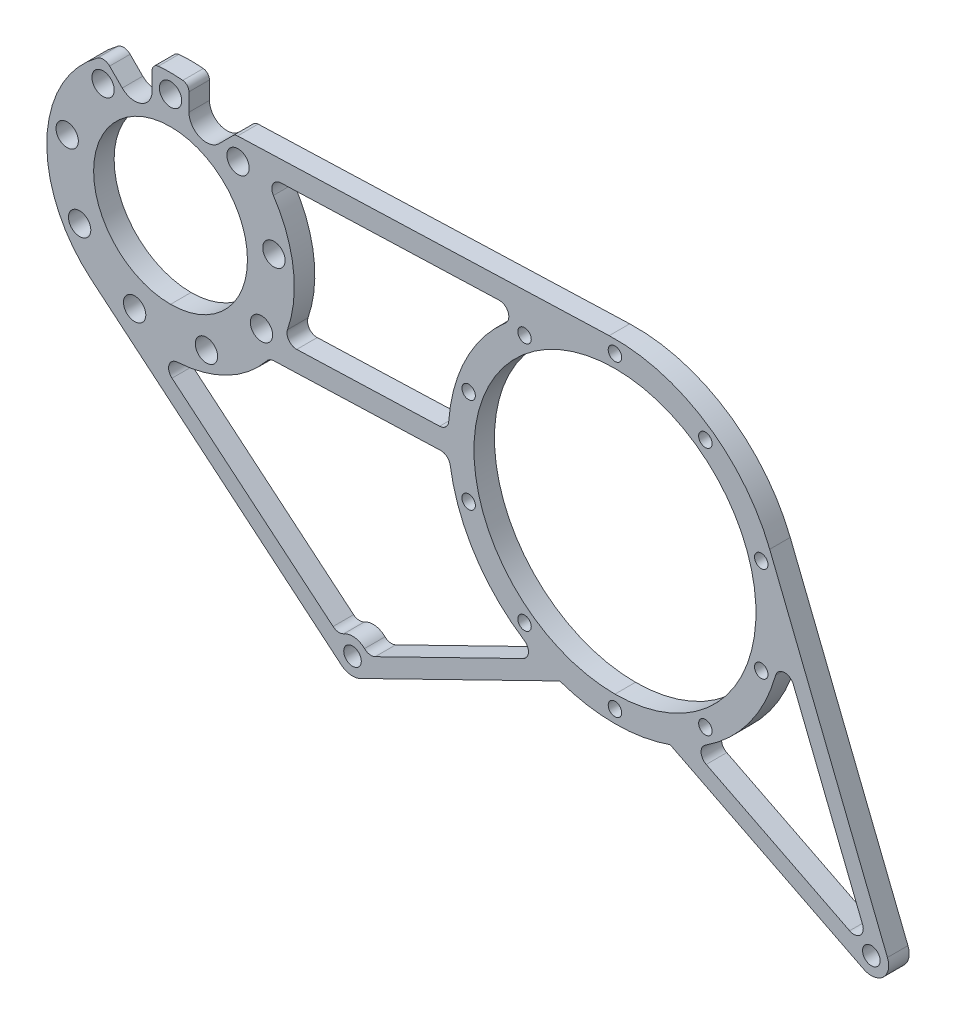
SolidWorks part; units mm, degrees
material "6061-T6 (SS)"
ref_plane "Front Plane" through (0, 0, 0) normal (0, 0, 1) x (1, 0, 0)
ref_plane "Top Plane" through (0, 0, 0) normal (0, 1, 0) x (1, 0, 0)
ref_plane "Right Plane" through (0, 0, 0) normal (1, 0, 0) x (0, 0, -1)
sketch "Sketch2" plane through (0, 0, 0) normal (0, 0, 1) x (1, 0, 0)
  line L0 (-114.3, 107.95) -> (-114.3, 95.25) construction
  line L1 (-308.8661, 91.7104) -> (-215.9264, 14.1075)
  line L3 (-13.0706, 21.4387) -> (-56.8054, 130.918)
  line L4 (-208.9705, 13.2659) -> (-134.815, 49.5352)
  line L5 (-21.9498, 13.301) -> (-93.785, 49.5352)
  line L7 (-254.4917, 165.0591) -> (-116.4363, 169.8256)
  line L10 (-286.2388, 170.2207) -> (-286.2388, 163.648)
  line L11 (-299.2388, 163.648) -> (-299.2388, 164.225)
  line L12 (-256.2001, 164.3167) -> (-261.465, 159.0518)
  line L13 (-272.5612, 163.648) -> (-272.5612, 170.2207)
  line L14 (-286.2388, 170.2207) -> (-286.2388, 163.648)
  line L16 (-256.2001, 164.3167) -> (-261.465, 159.0518)
  line L17 (-272.5612, 163.648) -> (-272.5612, 170.2207)
  line L84 (-302.5999, 164.3167) -> (-297.335, 159.0518) construction
  line L85 (-302.028, 163.7448) -> (-297.335, 159.0518)
  circle A0 centre (-279.4, 127) radius 28.575
  circle A1 centre (-114.3, 95.25) radius 36 construction
  circle A2 centre (0, 0) radius 12.7 construction
  circle A3 centre (-228.6, 0) radius 12.7 construction
  arc A5 (-134.815, 49.5352) -> (-93.785, 49.5352) centre (-114.3, 107.95) ccw
  circle A6 centre (-19.05, 19.05) radius 3.2639
  circle A7 centre (-211.7995, 19.05) radius 3.2639
  arc A8 (-215.9264, 14.1075) -> (-208.9705, 13.2659) centre (-211.7995, 19.05) ccw
  arc A9 (-21.9498, 13.301) -> (-13.0706, 21.4387) centre (-19.05, 19.05) ccw
  circle A10 centre (-114.3, 107.95) radius 52.3875
  arc A11 (-56.8054, 130.918) -> (-116.4363, 169.8256) centre (-114.3, 107.95) ccw
  arc A12 (-134.815, 49.5352) -> (-116.4363, 169.8256) centre (-114.3, 107.95) ccw construction
  arc A13 (-308.8661, 91.7104) -> (-306.5609, 164.0931) centre (-279.4, 127) cw
  arc A20 (-299.2388, 163.648) -> (-286.2388, 163.648) centre (-292.7388, 163.648) ccw
  arc A21 (-299.2388, 164.225) -> (-303.0875, 166.4019) centre (-301.7788, 164.225) ccw
  arc A22 (-303.0875, 166.4019) -> (-252.9423, 164.5979) centre (-279.4, 127) ccw
  arc A23 (-252.9423, 164.5979) -> (-256.2001, 164.3167) centre (-254.4041, 162.5207) ccw
  arc A24 (-272.5612, 163.648) -> (-261.465, 159.0518) centre (-266.0612, 163.648) ccw
  arc A25 (-272.5612, 170.2207) -> (-274.8498, 172.7483) centre (-275.1012, 170.2207) ccw
  arc A26 (-274.8498, 172.7483) -> (-283.9502, 172.7483) centre (-279.4, 127) ccw
  arc A27 (-283.9502, 172.7483) -> (-286.2388, 170.2207) centre (-283.6988, 170.2207) ccw
  arc A28 (-297.335, 159.0518) -> (-286.2388, 163.648) centre (-292.7388, 163.648) ccw
  arc A31 (-254.4917, 165.0591) -> (-256.2001, 164.3167) centre (-254.4041, 162.5207) ccw
  arc A32 (-272.5612, 163.648) -> (-261.465, 159.0518) centre (-266.0612, 163.648) ccw
  arc A33 (-272.5612, 170.2207) -> (-274.8498, 172.7483) centre (-275.1012, 170.2207) ccw
  arc A34 (-274.8498, 172.7483) -> (-283.9502, 172.7483) centre (-279.4, 127) ccw
  arc A35 (-283.9502, 172.7483) -> (-286.2388, 170.2207) centre (-283.6988, 170.2207) ccw
  arc A166 (-306.5609, 164.0931) -> (-302.028, 163.7448) centre (-304.4975, 161.2752) cw
  dimension "D1" = 25.4
  dimension "D2" = 25.4
  dimension "D8" = 57.15
  dimension "D9" = 72
  dimension "D10" = 3.4925
  dimension "D12" = 123.825
  dimension "D13" = 6.5278
  dimension "D16" = 6.5278
  dimension "D18" = 3.175
  dimension "D20" = 104.775
  dimension "D3" = 228.6
  dimension "D4" = 114.3
  dimension "D5" = 95.25
  dimension "D6" = 279.4
  dimension "D7" = 127
  dimension "D11" = 12.7
  dimension "D14" = 19.05
  dimension "D15" = 19.05
  dimension "D17" = 25.4
  dimension "D19" = 82.55
  dimension "D21" = 0
extrude "Boss-Extrude1" add sketch "Sketch2" along normal blind 7.62
sketch "Sketch3" plane through (0, 0, 7.62) normal (0, 0, 1) x (1, 0, 0)
  line L0 (-279.4, 127) -> (-279.4, 166) construction
  line L1 (-114.3, 107.95) -> (-114.3, 165.1) construction
  circle A0 centre (-279.4, 127) radius 39 construction
  circle A1 centre (-279.4, 166) radius 4.15
  circle A2 centre (-254.3313, 156.8757) radius 4.15
  circle A3 centre (-240.9925, 133.7723) radius 4.15
  circle A4 centre (-245.625, 107.5) radius 4.15
  circle A5 centre (-266.0612, 90.352) radius 4.15
  circle A6 centre (-292.7388, 90.352) radius 4.15
  circle A7 centre (-313.175, 107.5) radius 4.15
  circle A8 centre (-317.8075, 133.7723) radius 4.15
  circle A9 centre (-304.4687, 156.8757) radius 4.15
  circle A10 centre (-114.3, 107.95) radius 57.15 construction
  circle A11 centre (-114.3, 165.1) radius 2.5
  circle A12 centre (-80.7081, 154.1853) radius 2.5
  circle A13 centre (-59.9471, 125.6103) radius 2.5
  circle A14 centre (-59.9471, 90.2897) radius 2.5
  circle A15 centre (-80.7081, 61.7147) radius 2.5
  circle A16 centre (-114.3, 50.8) radius 2.5
  circle A17 centre (-147.8919, 61.7147) radius 2.5
  circle A18 centre (-168.6529, 90.2897) radius 2.5
  circle A19 centre (-168.6529, 125.6103) radius 2.5
  circle A20 centre (-147.8919, 154.1853) radius 2.5
  point P24 (-279.4, 127)
  point P27 (0, 0)
  point P48 (-114.3, 107.95)
  dimension "D1" = 78
  dimension "D2" = 8.3
  dimension "D4" = 114.3
  dimension "D5" = 5
  dimension "D3" = 9
  dimension "D6" = 10
extrude "Cut-Extrude1" cut sketch "Sketch3" against normal through all both and the other way through all
sketch "Sketch4" plane through (0, 0, 7.62) normal (0, 0, 1) x (1, 0, 0)
  line L0 (-278.8626, 74.9306) -> (-219.0181, 24.9616)
  line L1 (-48.0193, 91.8071) -> (-22.3039, 27.4349)
  line L2 (-308.8661, 91.7104) -> (-215.9264, 14.1075) construction
  line L3 (-148.3931, 49.9629) -> (-203.3792, 23.0694)
  line L4 (-208.9705, 13.2659) -> (-134.815, 49.5352) construction
  line L5 (-238.4024, 157.9901) -> (-157.3456, 160.7887)
  line L7 (-80.3879, 49.8896) -> (-27.12, 23.021)
  line L8 (-93.785, 49.5352) -> (-21.9498, 13.301) construction
  line L9 (-13.0706, 21.4387) -> (-56.8054, 130.918) construction
  line L10 (-232.5225, 107.3628) -> (-179.4127, 109.1965)
  line L11 (-241.009, 99.4453) -> (-179.0785, 101.5835)
  line L13 (-116.4363, 169.8256) -> (-254.4917, 165.0591) construction
  arc A0 (-235.9442, 111.9933) -> (-243.6076, 98.1468) centre (-279.4, 127) ccw construction
  arc A1 (-175.5054, 98.6194) -> (-176.0499, 112.434) centre (-114.3, 107.95) ccw construction
  circle A2 centre (-19.05, 19.05) radius 6.4389 construction
  circle A3 centre (-211.7995, 19.05) radius 6.4389 construction
  arc A4 (-306.5609, 164.0931) -> (-308.8661, 91.7104) centre (-279.4, 127) ccw construction
  arc A5 (-241.1849, 152.5581) -> (-235.9442, 111.9933) centre (-279.4, 127) cw
  arc A6 (-154.933, 154.6631) -> (-176.0499, 112.434) centre (-114.3, 107.95) ccw
  arc A7 (-54.6287, 91.4427) -> (-80.7099, 55.9417) centre (-114.3, 107.95) cw
  arc A8 (-157.3456, 160.7887) -> (-154.933, 154.6631) centre (-157.2251, 157.2982) cw
  arc A9 (-238.4024, 157.9901) -> (-241.1849, 152.5581) centre (-238.2818, 154.4997) ccw
  arc A10 (-278.8626, 74.9306) -> (-276.8202, 81.0984) centre (-276.6242, 77.6114) cw
  arc A11 (-148.0251, 56.0292) -> (-148.3931, 49.9629) centre (-149.9276, 53.1003) cw
  arc A12 (-80.3879, 49.8896) -> (-80.7099, 55.9417) centre (-78.8151, 53.0079) cw
  arc A13 (-48.0193, 91.8071) -> (-54.6287, 91.4427) centre (-51.2626, 90.5115) ccw
  arc A14 (-27.12, 23.021) -> (-22.3039, 27.4349) centre (-25.5472, 26.1393) ccw
  arc A15 (-215.0283, 24.6208) -> (-207.3352, 23.69) centre (-211.7995, 19.05) cw
  arc A16 (-203.3792, 23.0694) -> (-207.3352, 23.69) centre (-204.9137, 26.2067) cw
  arc A17 (-219.0181, 24.9616) -> (-215.0283, 24.6208) centre (-216.7797, 27.6425) ccw
  arc A18 (-243.6076, 98.1468) -> (-276.8202, 81.0984) centre (-279.4, 127) cw
  arc A19 (-175.5054, 98.6194) -> (-148.0251, 56.0292) centre (-114.3, 107.95) ccw
  arc A20 (-179.0785, 101.5835) -> (-175.5054, 98.6194) centre (-178.958, 98.0931) cw
  arc A21 (-179.4127, 109.1965) -> (-176.0499, 112.434) centre (-179.5332, 112.6869) ccw
  arc A22 (-232.5225, 107.3628) -> (-235.9442, 111.9933) centre (-232.643, 110.8533) cw
  arc A23 (-241.009, 99.4453) -> (-243.6076, 98.1468) centre (-240.8885, 95.9549) ccw
  point P40 (-245.2273, 157.7545)
  point P43 (-286.9003, 81.6419)
  point P46 (-142.5125, 52.8391)
  point P50 (-52.5701, 103.1988)
  point P56 (-216.7985, 23.1083)
  dimension "D1" = 61.9125
  dimension "D2" = 12.8778
  dimension "D3" = 12.8778
  dimension "D9" = 3.4925
  dimension "D10" = 61.9125
  dimension "D11" = 3.4925
  dimension "D14" = 3.4925
  dimension "D4" = 6.35
  dimension "D5" = 6.35
  dimension "D6" = 7.62
  dimension "D7" = 6.35
  dimension "D8" = 6.35
  dimension "D12" = 50.8
  dimension "D13" = 7.62
extrude "Cut-Extrude2" cut sketch "Sketch4" against normal through all both and the other way through all
sketch "Sketch6" plane through (0, 0, 7.62) normal (0, 0, 1) x (1, 0, 0)
  line L0 (-256.2001, 164.3171) -> (-261.465, 159.0522)
  line L1 (-272.5612, 163.6484) -> (-272.5612, 170.2212)
  line L2 (-286.2388, 170.2212) -> (-286.2388, 163.6484)
  line L3 (-299.2388, 163.6484) -> (-299.2392, 164.2676)
  arc A0 (-303.0807, 166.406) -> (-252.9493, 164.6028) centre (-279.4, 127) ccw
  arc A1 (-252.9493, 164.6028) -> (-256.2001, 164.3171) centre (-254.4043, 162.5208) ccw
  arc A2 (-272.5612, 163.6484) -> (-261.465, 159.0522) centre (-266.0612, 163.6484) ccw
  arc A3 (-272.5612, 170.2212) -> (-274.8498, 172.7487) centre (-275.1012, 170.2212) ccw
  arc A4 (-274.8498, 172.7487) -> (-283.9502, 172.7487) centre (-279.4, 127.0004) ccw
  arc A5 (-283.9502, 172.7487) -> (-286.2388, 170.2212) centre (-283.6988, 170.2212) ccw
  arc A6 (-299.2388, 163.6484) -> (-286.2388, 163.6484) centre (-292.7388, 163.6484) ccw
  arc A7 (-299.2392, 164.2676) -> (-303.0807, 166.406) centre (-301.7788, 164.225) ccw
  point P20 (0, 0)
  dimension "D1" = 45.974
  dimension "D2" = 2.54
  dimension "D4" = 6.5
  dimension "D5" = 6.5
  dimension "D6" = 2.54
  dimension "D7" = 2.54
  dimension "D8" = 45.974
  dimension "D9" = 2.54
  dimension "D3" = 7.4457
  dimension "D10" = 6.5727
ref_plane "Plane3" through (0, 0, 3.81) normal (0, 0, 1) x (1, 0, 0)
ref_axis "Axis1" through (-279.4, 127, 7.62) along (0, 0, -1)
ref_plane "Plane1" through (-279.4, 0, 0) normal (1, 0, 0) x (0, 0, -1)
ref_axis "Axis2" through (-114.3, 107.95, 7.62) along (0, 0, -1)
ref_plane "Plane2" through (-114.3, 0, 0) normal (1, 0, 0) x (0, 0, -1)
split line "Split Line1"
split line "Split Line2"
sketch "Sketch7" plane through (0, 0, 3.81) normal (0, 0, 1) x (1, 0, 0)
  arc A0 (-279.4, 155.575) -> (-279.4, 98.425) centre (-279.4, 127) ccw construction
  arc A1 (-279.4, 98.425) -> (-279.4, 155.575) centre (-279.4, 127) ccw construction
  arc A2 (-279.4, 155.575) -> (-279.4, 98.425) centre (-279.4, 127) ccw
  arc A3 (-279.4, 98.425) -> (-279.4, 155.575) centre (-279.4, 127) ccw
  arc A4 (-114.3, 55.5625) -> (-114.3, 160.3375) centre (-114.3, 107.95) ccw construction
  arc A5 (-114.3, 160.3375) -> (-114.3, 55.5625) centre (-114.3, 107.95) ccw construction
  arc A6 (-114.3, 55.5625) -> (-114.3, 160.3375) centre (-114.3, 107.95) ccw
  arc A7 (-114.3, 160.3375) -> (-114.3, 55.5625) centre (-114.3, 107.95) ccw
  point P4 (-279.4, 127)
  point P8 (-114.3, 107.95)
